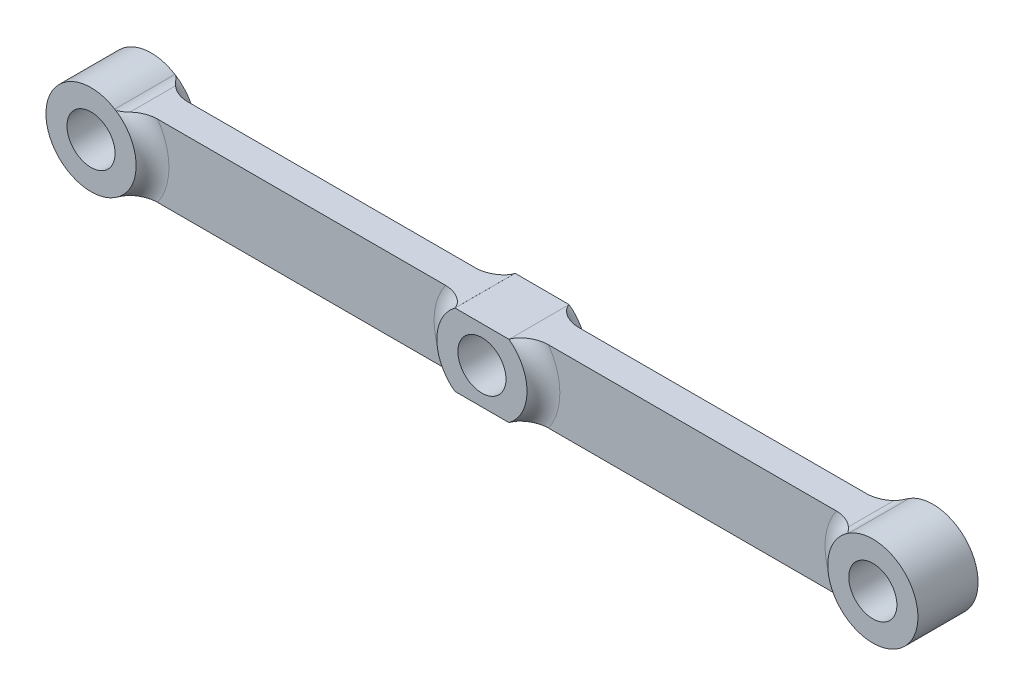
SolidWorks part; units mm, degrees
ref_plane "前视基准面" through (0, 0, 0) normal (0, 0, 1) x (1, 0, 0)
ref_plane "上视基准面" through (0, 0, 0) normal (0, 1, 0) x (1, 0, 0)
ref_plane "右视基准面" through (0, 0, 0) normal (1, 0, 0) x (0, 0, -1)
sketch "草图1" plane through (0, 0, 0) normal (0, 0, 1) x (1, 0, 0)
  line L0 (0, 0) -> (-65, 0) construction
  line L1 (59.7322, 6) -> (-59.7322, 6)
  line L2 (59.7322, -6) -> (-59.7322, -6)
  line L3 (0, -6) -> (0, 73.9405) construction
  arc A0 (-61.0491, 6.375) -> (-61.0491, -6.375) centre (-65, 0) ccw
  arc A1 (-61.0491, 6.375) -> (-59.7322, 6) centre (-59.7322, 8.5) ccw
  arc A2 (-61.0491, -6.375) -> (-59.7322, -6) centre (-59.7322, -8.5) cw
  arc A3 (61.0491, 6.375) -> (61.0491, -6.375) centre (65, 0) cw
  arc A4 (61.0491, -6.375) -> (59.7322, -6) centre (59.7322, -8.5) ccw
  arc A5 (61.0491, 6.375) -> (59.7322, 6) centre (59.7322, 8.5) cw
  point P16 (0, 6)
  dimension "D3" = 15
  dimension "D4" = 5
  dimension "D1" = 65
  dimension "D2" = 6
extrude "凸台-拉伸1" add sketch "草图1" along normal blind 5
sketch "草图2" plane through (0, 0, 5) normal (0, 0, 1) x (1, 0, 0)
  circle A0 centre (-65, 0) radius 4
  circle A1 centre (65, 0) radius 4
  circle A2 centre (0, 0) radius 4
  dimension "D1" = 8
  dimension "D2" = 8
  dimension "D3" = 8
extrude "切除-拉伸1" cut sketch "草图2" against normal blind 5
ref_plane "基准面1" through (0, 0, 2.5) normal (0, 0, 1) x (1, 0, 0)
sketch "草图3" plane through (0, 0, 2.5) normal (0, 0, 1) x (1, 0, 0)
  line L0 (-4.4722, 6.0207) -> (4.5, 6)
  line L1 (59.7322, 6) -> (-59.7322, 6) construction
  line L2 (-4.5, -6) -> (4.5, -6)
  line L3 (-59.7322, -6) -> (59.7322, -6) construction
  arc A0 (-61.0491, 6.375) -> (-61.0491, -6.375) centre (-65, 0) ccw construction
  circle A1 centre (-65, 0) radius 4 construction
  arc A2 (-61.0491, 6.375) -> (-61.0491, -6.375) centre (-65, 0) ccw
  circle A3 centre (-65, 0) radius 4
  arc A4 (-61.0491, 6.375) -> (-61.0491, -6.375) centre (-65, 0) cw
  arc A5 (61.0491, -6.375) -> (61.0491, 6.375) centre (65, 0) ccw construction
  circle A6 centre (65, 0) radius 4 construction
  arc A7 (61.0491, -6.375) -> (61.0491, 6.375) centre (65, 0) ccw
  circle A8 centre (65, 0) radius 4
  arc A9 (61.0491, 6.375) -> (61.0491, -6.375) centre (65, 0) ccw
  circle A10 centre (0, 0) radius 4 construction
  circle A11 centre (0, 0) radius 4
  arc A12 (-4.4722, 6.0207) -> (-4.5, -6) centre (0, 0) ccw
  arc A13 (4.5, -6) -> (4.5, 6) centre (0, 0) ccw
  dimension "D1" = 15
extrude "凸台-拉伸2" add sketch "草图3" along normal mid plane 10
fillet "圆角1" radius 3 8 edges at (57.5, 0, 0) (57.5, 0, 5) (7.5, 0, 5) (-7.5, 0, 5) (-7.5, 0, 0) (7.5, 0, 0) (-57.5, 0, 0) (-57.5, 0, 5)
